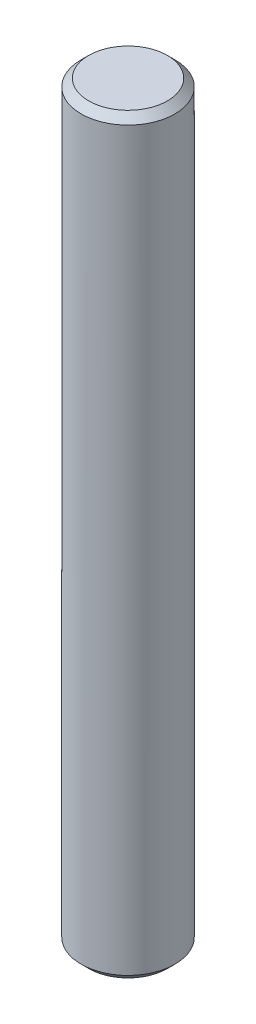
SolidWorks part; units mm, degrees
material "AISI 303 Stainless"
ref_plane "Front Plane" through (0, 0, 0) normal (0, 0, 1) x (1, 0, 0)
ref_plane "Top Plane" through (0, 0, 0) normal (0, 1, 0) x (1, 0, 0)
ref_plane "Right Plane" through (0, 0, 0) normal (1, 0, 0) x (0, 0, -1)
other "Configuration Table"
sketch "Sketch1" plane through (0, 0, 0) normal (0, 0, 1) x (1, 0, 0)
  line L0 (3.1712, 50.8) -> (0, 50.8)
  line L1 (0, 50.8) -> (0, 0)
  line L2 (0, 0) -> (3.1712, 0)
  line L3 (3.1712, 0) -> (3.1712, 50.8)
  line L4 (0, 50.8) -> (0, 0) construction
  dimension "D1" = 3.1712
  dimension "D2" = 50.8
revolve "Revolve1" add sketch "Sketch1" angle 360 about L4 reverse direction yes
chamfer "Chamfer1" distance 0.508 angle 45 1 edges at (0, 0, -3.1712)
chamfer "Chamfer2" distance 0.508 angle 45 1 edges at (0, 50.8, -3.1712)
ref_point "Point2"
